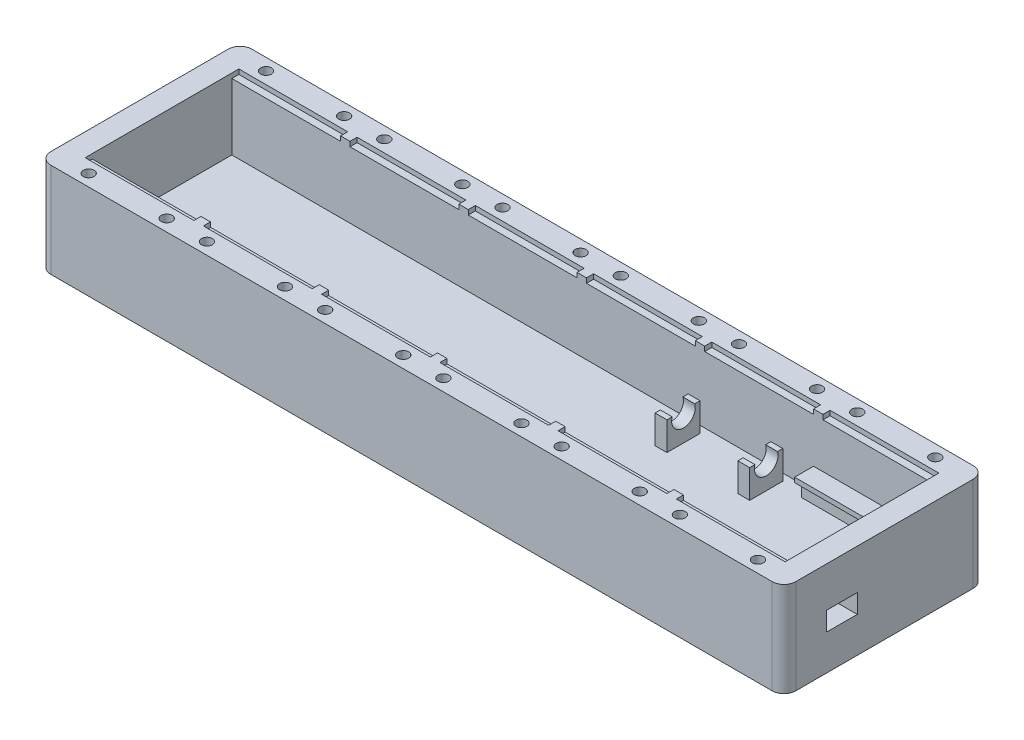
SolidWorks part; units mm, degrees
material "Starkstromplatine"
ref_plane "Ebene vorne" through (0, 0, 0) normal (0, 0, 1) x (1, 0, 0)
ref_plane "Ebene oben" through (0, 0, 0) normal (0, 1, 0) x (1, 0, 0)
ref_plane "Ebene rechts" through (0, 0, 0) normal (1, 0, 0) x (0, 0, -1)
sketch "Skizze2" plane through (0, 0, 0) normal (0, 0, 1) x (1, 0, 0)
  line L1 (0, 0) -> (315, 0)
  line L2 (0, 0) -> (0, 40)
  line L3 (0, 40) -> (315, 40)
  line L4 (315, 0) -> (315, 40)
  dimension "D1" = 315
  dimension "D2" = 40
extrude "Aufsatz-Linear austragen1" add sketch "Skizze2" along normal blind 85
sketch "Skizze4" plane through (0, 40, 0) normal (0, 1, 0) x (1, 0, 0)
  line L1 (9.5, -13) -> (305.5, -13)
  line L2 (9.5, -13) -> (9.5, -72)
  line L3 (9.5, -72) -> (305.5, -72)
  line L4 (305.5, -13) -> (305.5, -72)
  line L6 (0, -85) -> (0, 0) construction
  line L7 (315, -85) -> (315, 0) construction
  line L8 (315, -85) -> (0, -85) construction
  dimension "D1" = 59
  dimension "D2" = 13
  dimension "D3" = 9.5
  dimension "D4" = 9.5
extrude "Schnitt-Linear austragen1" cut sketch "Skizze4" against normal blind 30
sketch "Skizze11" plane through (0, 40, 0) normal (0, 1, 0) x (1, 0, 0)
  line L0 (9.5, -72) -> (305.5, -72) construction
  line L1 (9.5, -13) -> (55.5, -13)
  line L2 (9.5, -13) -> (9.5, -10)
  line L3 (9.5, -10) -> (55.5, -10)
  line L4 (55.5, -13) -> (55.5, -10)
  line L5 (55.5, -72) -> (9.5, -72)
  line L6 (55.5, -72) -> (55.5, -75)
  line L7 (55.5, -75) -> (9.5, -75)
  line L8 (9.5, -72) -> (9.5, -75)
  line L9 (305.5, -13) -> (9.5, -13) construction
  line L10 (59.5, -75) -> (105.5, -75)
  line L11 (59.5, -75) -> (59.5, -72)
  line L12 (59.5, -72) -> (105.5, -72)
  line L13 (105.5, -75) -> (105.5, -72)
  line L14 (109.5, -75.0087) -> (155.5, -75.0087)
  line L15 (109.5, -75.0087) -> (109.5, -72)
  line L16 (109.5, -72) -> (155.5, -72)
  line L17 (155.5, -75.0087) -> (155.5, -72)
  line L18 (159.5, -75.0087) -> (205.5, -75.0087)
  line L19 (159.5, -75.0087) -> (159.5, -72)
  line L20 (159.5, -72) -> (205.5, -72)
  line L21 (205.5, -75.0087) -> (205.5, -72)
  line L22 (209.5, -75) -> (255.5, -75)
  line L23 (209.5, -75) -> (209.5, -72)
  line L24 (209.5, -72) -> (255.5, -72)
  line L25 (255.5, -75) -> (255.5, -72)
  line L26 (259.5, -75) -> (305.5, -75)
  line L27 (259.5, -75) -> (259.5, -72)
  line L28 (259.5, -72) -> (305.5, -72)
  line L29 (305.5, -75) -> (305.5, -72)
  line L30 (305.5, -13) -> (259.5, -13)
  line L31 (305.5, -13) -> (305.5, -10)
  line L32 (305.5, -10) -> (259.5, -10)
  line L33 (259.5, -13) -> (259.5, -10)
  line L35 (255.5, -13) -> (209.5, -13)
  line L36 (255.5, -13) -> (255.5, -10)
  line L37 (255.5, -10) -> (209.5, -10)
  line L38 (209.5, -13) -> (209.5, -10)
  line L39 (205.5, -13) -> (159.5, -13)
  line L40 (205.5, -13) -> (205.5, -10)
  line L41 (205.5, -10) -> (159.5, -10)
  line L42 (159.5, -13) -> (159.5, -10)
  line L43 (155.5, -13) -> (109.5, -13)
  line L44 (155.5, -13) -> (155.5, -10)
  line L45 (155.5, -10) -> (109.5, -10)
  line L46 (109.5, -13) -> (109.5, -10)
  line L47 (105.5, -13) -> (59.5, -13)
  line L48 (105.5, -13) -> (105.5, -10)
  line L49 (105.5, -10) -> (59.5, -10)
  line L50 (59.5, -13) -> (59.5, -10)
  line L56 (315, -85) -> (315, 0) construction
  dimension "D1" = 46
  dimension "D2" = 3
  dimension "D3" = 46
  dimension "D4" = 4
  dimension "D5" = 4
  dimension "D6" = 4
  dimension "D7" = 4
  dimension "D8" = 4
  dimension "D9" = 4
  dimension "D10" = 46
  dimension "D11" = 46
  dimension "D12" = 46
  dimension "D13" = 46
  dimension "D14" = 46
  dimension "D15" = 4
  dimension "D16" = 4
  dimension "D17" = 4
  dimension "D18" = 4
  dimension "D19" = 46
  dimension "D20" = 46
  dimension "D21" = 46
  dimension "D22" = 46
  dimension "D23" = 3
  dimension "D24" = 3
  dimension "D25" = 3
  dimension "D26" = 3
  dimension "D27" = 3
  dimension "D28" = 3
  dimension "D29" = 3
  dimension "D30" = 3
  dimension "D31" = 46
  dimension "D32" = 9.5
extrude "Schnitt-Linear austragen4" cut sketch "Skizze11" against normal blind 2
sketch "Skizze17" plane through (0, 40, 0) normal (0, 1, 0) x (1, 0, 0)
  line L0 (55.5, -75) -> (55.5, -72) construction
  line L1 (315, 0) -> (0, 0) construction
  line L2 (315, -85) -> (0, -85) construction
  line L3 (9.5, -72) -> (9.5, -75) construction
  line L4 (9.5, -10) -> (9.5, -75) construction
  line L5 (55.5, -13) -> (55.5, -10) construction
  line L6 (59.5, -72) -> (59.5, -75) construction
  line L7 (105.5, -75) -> (105.5, -72) construction
  line L8 (155.5, -75.0087) -> (155.5, -72) construction
  line L9 (105.5, -13) -> (105.5, -10) construction
  line L10 (159.5, -72) -> (159.5, -75.0087) construction
  line L11 (205.5, -75.0087) -> (205.5, -72) construction
  line L12 (305.5, -75) -> (305.5, -10) construction
  line L13 (259.5, -72) -> (259.5, -75) construction
  line L14 (255.5, -75) -> (255.5, -72) construction
  line L15 (209.5, -72) -> (209.5, -75) construction
  line L16 (59.5, -10) -> (59.5, -13) construction
  line L17 (155.5, -13) -> (155.5, -10) construction
  line L18 (109.5, -10) -> (109.5, -13) construction
  line L19 (159.5, -10) -> (159.5, -13) construction
  line L20 (209.5, -10) -> (209.5, -13) construction
  line L21 (255.5, -13) -> (255.5, -10) construction
  line L22 (259.5, -10) -> (259.5, -13) construction
  line L23 (305.5, -13) -> (305.5, -10) construction
  line L24 (109.5, -72) -> (109.5, -75.0087) construction
  circle A0 centre (49, -80) radius 2.3
  circle A1 centre (16, -80) radius 2.3
  circle A2 centre (16, -5) radius 2.3
  circle A3 centre (49, -5) radius 2.3
  circle A4 centre (66, -5) radius 2.3
  circle A5 centre (99, -5) radius 2.3
  circle A6 centre (66, -80) radius 2.3
  circle A7 centre (99, -80) radius 2.3
  circle A8 centre (116, -80) radius 2.3
  circle A9 centre (149, -80) radius 2.3
  circle A10 centre (166, -80) radius 2.3
  circle A11 centre (199, -80) radius 2.3
  circle A12 centre (216, -80) radius 2.3
  circle A13 centre (249, -80) radius 2.3
  circle A14 centre (266, -80) radius 2.3
  circle A15 centre (299, -80) radius 2.3
  circle A16 centre (299, -5) radius 2.3
  circle A17 centre (266, -5) radius 2.3
  circle A18 centre (249, -5) radius 2.3
  circle A19 centre (216, -5) radius 2.3
  circle A20 centre (199, -5) radius 2.3
  circle A21 centre (166, -5) radius 2.3
  circle A22 centre (149, -5) radius 2.3
  circle A23 centre (116, -5) radius 2.3
  dimension "D1" = 4.6
  dimension "D2" = 4.6
  dimension "D3" = 4.6
  dimension "D4" = 4.6
  dimension "D5" = 5
  dimension "D6" = 5
  dimension "D7" = 5
  dimension "D8" = 5
  dimension "D10" = 6.5
  dimension "D11" = 6.5
  dimension "D12" = 6.5
  dimension "D13" = 4.6
  dimension "D14" = 4.6
  dimension "D15" = 4.6
  dimension "D16" = 4.6
  dimension "D17" = 4.6
  dimension "D18" = 4.6
  dimension "D19" = 4.6
  dimension "D20" = 4.6
  dimension "D21" = 4.6
  dimension "D22" = 4.6
  dimension "D23" = 6.5
  dimension "D25" = 5
  dimension "D26" = 5
  dimension "D27" = 6.5
  dimension "D28" = 5
  dimension "D29" = 6.5
  dimension "D30" = 5
  dimension "D31" = 6.5
  dimension "D32" = 5
  dimension "D33" = 5
  dimension "D34" = 5
  dimension "D35" = 5
  dimension "D36" = 5
  dimension "D37" = 6.5
  dimension "D38" = 6.5
  dimension "D39" = 6.5
  dimension "D40" = 6.5
  dimension "D41" = 5
  dimension "D42" = 6.5
  dimension "D43" = 4.6
  dimension "D44" = 4.6
  dimension "D45" = 4.6
  dimension "D46" = 4.6
  dimension "D47" = 4.6
  dimension "D48" = 4.6
  dimension "D49" = 4.6
  dimension "D50" = 4.6
  dimension "D51" = 4.6
  dimension "D52" = 4.6
  dimension "D53" = 5
  dimension "D54" = 6.5
  dimension "D55" = 5
  dimension "D56" = 6.5
  dimension "D58" = 6.5
  dimension "D62" = 6.5
  dimension "D63" = 6.5
  dimension "D64" = 6.5
  dimension "D9" = 6.5
  dimension "D24" = 6.5
  dimension "D57" = 6.5
  dimension "D59" = 6.5
  dimension "D60" = 6.5
  dimension "D61" = 6.5
extrude "Schnitt-Linear austragen6" cut sketch "Skizze17" against normal blind 4
fillet "Verrundung2" radius 5 1 edges at (0, 20, 85)
fillet "Verrundung3" radius 5 1 edges at (0, 20, 0)
fillet "Verrundung4" radius 5 1 edges at (315, 20, 0)
fillet "Verrundung6" radius 5 1 edges at (315, 20, 85)
sketch "Skizze18" plane through (305.5, 0, 0) normal (-1, 0, 0) x (0, 0, 1)
  line L0 (72, 10) -> (72, 38) construction
  line L1 (54, 23) -> (67, 23)
  line L2 (54, 23) -> (54, 15)
  line L3 (54, 15) -> (67, 15)
  line L4 (67, 23) -> (67, 15)
  line L5 (72, 10) -> (13, 10) construction
  dimension "D1" = 5
  dimension "D2" = 13
  dimension "D3" = 8
  dimension "D4" = 5
  dimension "D5" = 5
extrude "Schnitt-Linear austragen7" cut sketch "Skizze18" against normal blind 10
sketch "Skizze20" plane through (0, 10, 0) normal (0, 1, 0) x (1, 0, 0)
  line L0 (305.5, -13) -> (9.5, -13) construction
  line L1 (240.5, -16) -> (245.5, -16)
  line L2 (240.5, -16) -> (240.5, -30)
  line L3 (240.5, -30) -> (245.5, -30)
  line L4 (245.5, -16) -> (245.5, -30)
  line L5 (205.5, -16) -> (210.5, -16)
  line L6 (205.5, -16) -> (205.5, -30)
  line L7 (205.5, -30) -> (210.5, -30)
  line L8 (210.5, -16) -> (210.5, -30)
  line L9 (305.5, -72) -> (305.5, -13) construction
  dimension "D1" = 14
  dimension "D2" = 14
  dimension "D3" = 5
  dimension "D4" = 5
  dimension "D5" = 3
  dimension "D6" = 3
  dimension "D7" = 30
  dimension "D8" = 60
extrude "Aufsatz-Linear austragen2" add sketch "Skizze20" along normal blind 12
sketch "Skizze21" plane through (205.5, 0, 0) normal (-1, 0, 0) x (0, 0, 1)
  line L0 (16, 22) -> (16, 10) construction
  line L1 (16, 22) -> (30, 22) construction
  circle A0 centre (23, 20.5) radius 5
  dimension "D1" = 7
  dimension "D2" = 1.5
extrude "Schnitt-Linear austragen8" cut sketch "Skizze21" against normal blind 71
sketch "Skizze22" plane through (0, 0, 13) normal (0, 0, 1) x (1, 0, 0)
  line L0 (305.5, 10) -> (305.5, 38) construction
  line L1 (305.5, 10) -> (255.5, 10)
  line L2 (305.5, 10) -> (305.5, 19)
  line L3 (305.5, 19) -> (255.5, 19)
  line L4 (255.5, 10) -> (255.5, 19)
  line L5 (305.5, 10) -> (9.5, 10) construction
  dimension "D1" = 0
  dimension "D2" = 9
  dimension "D3" = 50
extrude "Aufsatz-Linear austragen3" add sketch "Skizze22" along normal blind 5
sketch "Skizze23" plane through (0, 0, 18) normal (0, 0, 1) x (1, 0, 0)
  line L0 (305.5, 10) -> (305.5, 19) construction
  line L1 (255.5, 19) -> (305.5, 19)
  line L2 (255.5, 19) -> (255.5, 17)
  line L3 (255.5, 17) -> (305.5, 17)
  line L4 (305.5, 19) -> (305.5, 17)
  line L5 (255.5, 10) -> (305.5, 10) construction
  line L6 (305.5, 19) -> (255.5, 19) construction
  line L7 (9.5, 10) -> (305.5, 10) construction
  dimension "D1" = 2
extrude "Aufsatz-Linear austragen4" add sketch "Skizze23" along normal blind 3
